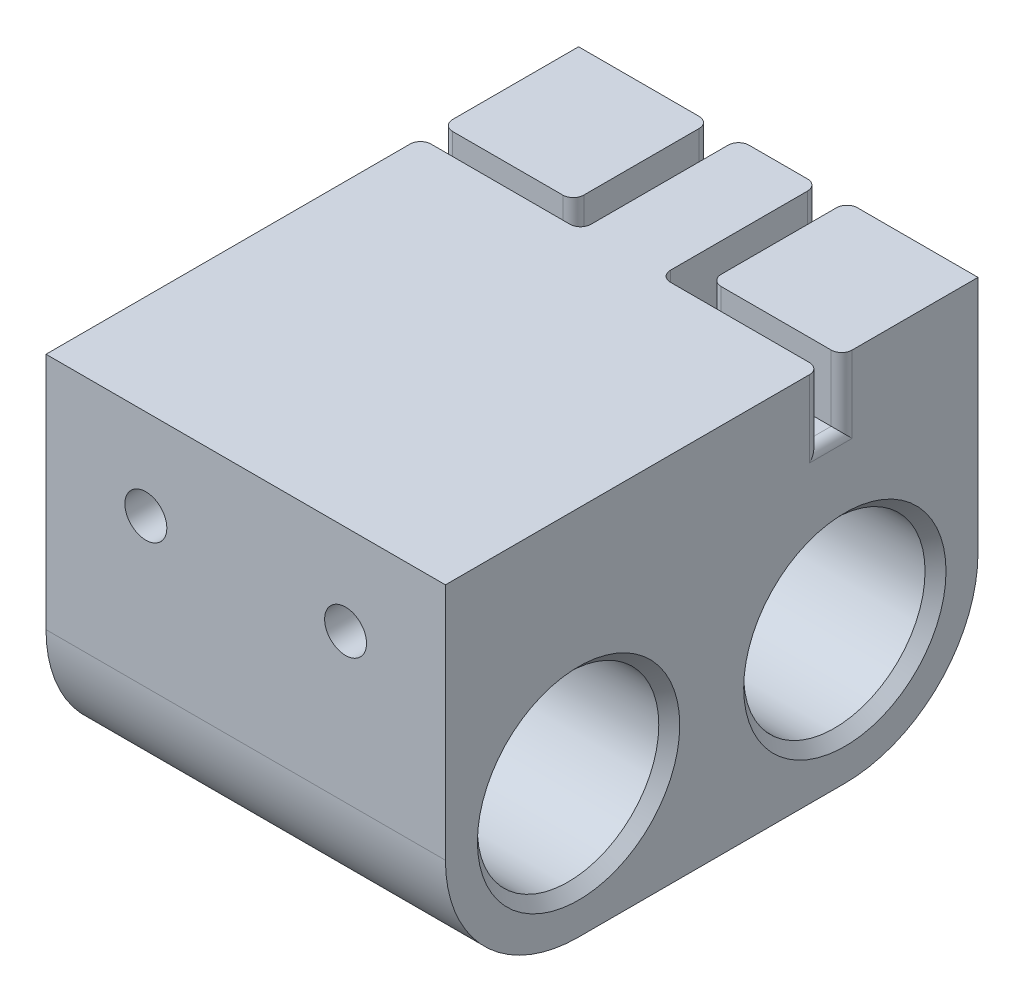
SolidWorks part; units mm, degrees
ref_plane "Front Plane" through (0, 0, 0) normal (0, 0, 1) x (1, 0, 0)
ref_plane "Top Plane" through (0, 0, 0) normal (0, 1, 0) x (1, 0, 0)
ref_plane "Right Plane" through (0, 0, 0) normal (1, 0, 0) x (0, 0, -1)
sketch "Sketch1" plane through (0, 0, 0) normal (1, 0, 0) x (0, 0, -1)
  line L0 (25.4, 22.75) -> (25.4, 0) construction
  line L1 (0, 22.75) -> (50.8, 22.75)
  line L2 (0, 22.75) -> (0, 0)
  line L3 (0, 0) -> (50.8, 0)
  line L4 (50.8, 22.75) -> (50.8, 0)
  circle A0 centre (12.7, 0) radius 8.65
  circle A1 centre (38.1, 0) radius 8.65
  circle A2 centre (12.7, 0) radius 12.7
  circle A3 centre (38.1, 0) radius 12.7
  dimension "D1" = 17.3
  dimension "D6" = 25.4
  dimension "D2" = 25.4
  dimension "D3" = 50.8
  dimension "D4" = 12.7
  dimension "D5" = 22.75
extrude "Boss-Extrude2" add sketch "Sketch1" along normal blind 38.1 contours L3 A2 A0 | L3 A2 A0 | L3 A3 A1 | L3 A3 A1 | L1 L0 L3 A3 L4 | L0 L1 L2 L3 A2 region at (0, 16.0478, -25.4) region at (0, 12.416, -12.7) region at (0, -0.284, -2.025) region at (0, -12.416, -38.1) region at (0, 0.284, -48.775)
ref_plane "Plane1" through (0, -12.7, 0) normal (0, -1, 0) x (-1, 0, 0)
sketch "Sketch6" plane through (0, -12.7, 0) normal (0, -1, 0) x (-1, 0, 0)
  line L0 (-38.1, 38.1) -> (0, 38.1)
  line L1 (-38.1, 50.8) -> (-38.1, 25.4) construction
  line L2 (0, 25.4) -> (0, 50.8) construction
  line L3 (-38.1, 12.7) -> (0, 12.7)
  line L4 (-38.1, 25.4) -> (-38.1, 0) construction
  line L5 (0, 0) -> (0, 25.4) construction
  line L7 (-38.1, 38.1) -> (0, 38.1)
  line L8 (-38.1, 38.1) -> (-38.1, 12.7)
  line L9 (-38.1, 12.7) -> (0, 12.7)
  line L10 (0, 38.1) -> (0, 12.7)
  circle A0 centre (-19.05, 38.1) radius 2
  circle A1 centre (-19.05, 12.7) radius 2
  dimension "D1" = 4
extrude "Cut-Extrude5" cut sketch "Sketch6" against normal up to next contours A0 | A1
extrude "Boss-Extrude3" add sketch "Sketch6<3>" against normal up to next contours A1 L3 L10 L0 A0 L8 region at (19.05, -12.7, -25.4)
sketch "Sketch6<3>" plane through (0, -12.7, 0) normal (0, -1, 0) x (-1, 0, 0) same geometry as "Sketch6"
sketch "Sketch10" plane through (0, 0, 0) normal (0, 0, 1) x (1, 0, 0)
  line L0 (38.1, 22.75) -> (38.1, 0) construction
  line L1 (0, 22.75) -> (38.1, 22.75)
  line L2 (0, 22.75) -> (0, 5.5563)
  line L3 (0, 5.5563) -> (38.1, 5.5563)
  line L4 (38.1, 22.75) -> (38.1, 5.5563)
  line L5 (19.05, 22.75) -> (19.05, 5.5563) construction
  line L6 (0, 14.1531) -> (19.05, 14.1531) construction
  line L7 (19.05, 14.1531) -> (38.1, 14.1531) construction
  circle A0 centre (9.525, 14.1531) radius 2
  circle A1 centre (28.575, 14.1531) radius 2
  dimension "D2" = 4
  dimension "D1" = 17.1937
extrude "Cut-Extrude6" cut sketch "Sketch10" against normal blind 8 contours A0 | A1 region at (9.525, 14.1531, 0) region at (28.575, 14.1531, 0)
chamfer "Chamfer1" distance 1 angle 45 4 edges at (38.1, 0, -21.35) (38.1, 0, -46.75) (0, 0, -21.35) (0, 0, -46.75)
sketch "Sketch15" plane through (0, 22.75, 0) normal (0, 1, 0) x (1, 0, 0)
  line L0 (0, 50.8) -> (38.1, 50.8) construction
  line L5 (0, 37.795) -> (12.5, 37.795)
  line L6 (12.5, 37.795) -> (12.5, 50.8)
  line L8 (15.26, 50.8) -> (15.26, 35.725)
  line L9 (15.26, 35.725) -> (0, 35.725)
  line L11 (0, 36.76) -> (15.26, 36.76) construction
  line L12 (19.05, 25.4) -> (19.05, 50.8) construction
  line L13 (13.88, 50.8) -> (13.88, 35.725) construction
  line L14 (22.84, 35.725) -> (38.1, 35.725)
  line L15 (22.84, 50.8) -> (22.84, 35.725)
  line L17 (25.6, 37.795) -> (25.6, 50.8)
  line L18 (38.1, 37.795) -> (25.6, 37.795)
  line L20 (0, 50.8) -> (38.1, 50.8)
  line L21 (0, 50.8) -> (0, 25.4)
  line L22 (0, 25.4) -> (38.1, 25.4)
  line L23 (38.1, 50.8) -> (38.1, 25.4)
  line L25 (0, 35.725) -> (0, 25.4) construction
  point P22 (0, 0)
  point P27 (0, 0)
  line M70 (0, 50.8) -> (0, 0)
  line M72 (38.1, 0) -> (38.1, 50.8)
  line M73 (38.1, 50.8) -> (0, 50.8)
  dimension "D1" = 25.4
  dimension "D2" = 2.07
  dimension "D6" = 11.36
  dimension "D3" = 2.76
  dimension "D4" = 15.26
  dimension "D5" = 12.5
  dimension "D7" = 38.1
extrude "Cut-Extrude9" cut sketch "Sketch15" against normal blind 6.3 contours L9 L8 L6 L5 M73 M70 | L18 L17 L15 L14 M72 M73 region at (6.25, 22.75, -37.5805) region at (24.22, 22.75, -50.5855)
fillet "Fillet3" radius 1 16 edges at (25.6, 19.6, -37.795) (22.84, 19.6, -35.725) (15.26, 19.6, -35.725) (12.5, 19.6, -37.795) (38.1, 19.6, -35.725) (38.1, 16.45, -36.76) (38.1, 19.6, -37.795) (25.6, 19.6, -50.8) (24.22, 16.45, -50.8) (22.84, 19.6, -50.8) (15.26, 19.6, -50.8) (13.88, 16.45, -50.8) (12.5, 19.6, -50.8) (0, 19.6, -37.795) (0, 16.45, -36.76) (0, 19.6, -35.725)
equation "\"Ø Smaller Shaft\"=6.35"
equation "\"Shaft Distance\"= 25.4"
equation "\"Width\"= \"Ø Smaller Shaft\" * 2 + \"Shaft Distance\" + \"Width End\" * 2"
equation "\"Width End\"= 6.35"
equation "\"Length\"= 38.1"
equation "\"Rod to Belt\"= 31.75 + 3"
equation "\"Nom Tolerance\"= 0.15"
equation "\"D1@Sketch1\"=\"Ø Graphite Holder\" + \"Nom Tolerance\"*2"
equation "\"D2@Sketch1\"=\"Shaft Distance\""
equation "\"D3@Sketch1\"= \"Width\""
equation "\"D4@Sketch1\"=\"Shaft Distance\"/2"
equation "\"Belt\"= 6"
equation "\"Belt Thickness\"=1.38"
equation "\"Ø Pulley\"= 10.9"
equation "\"Pully Distance\"= 35"
equation "\"D6@Sketch1\"=\"Ø Smaller Shaft\"*4"
equation "\"D5@Sketch1\"=\"Rod to Belt\"+(\"Belt\"/2)-15"
equation "\"D1@Boss-Extrude2\"=\"Length\""
equation "\"Ø Outer Washer\"=12.7"
equation "\"Washer Thickness\"=2"
equation "\"D1\" = \"Washer Thickness\""
equation "\"M3 Heated Insert Hole\"= 4"
equation "\"D1@Sketch6\"=\"M3 Heated Insert Hole\""
equation "\"D1@Sketch10\"=\"Rod to Belt\"+(\"Belt\"/2)-15-(\"Ø Smaller Shaft\"*1.75)/2"
equation "\"D2@Sketch10\"=\"M3 Heated Insert Hole\""
equation "\"Ø Graphite Holder\"= 17"
